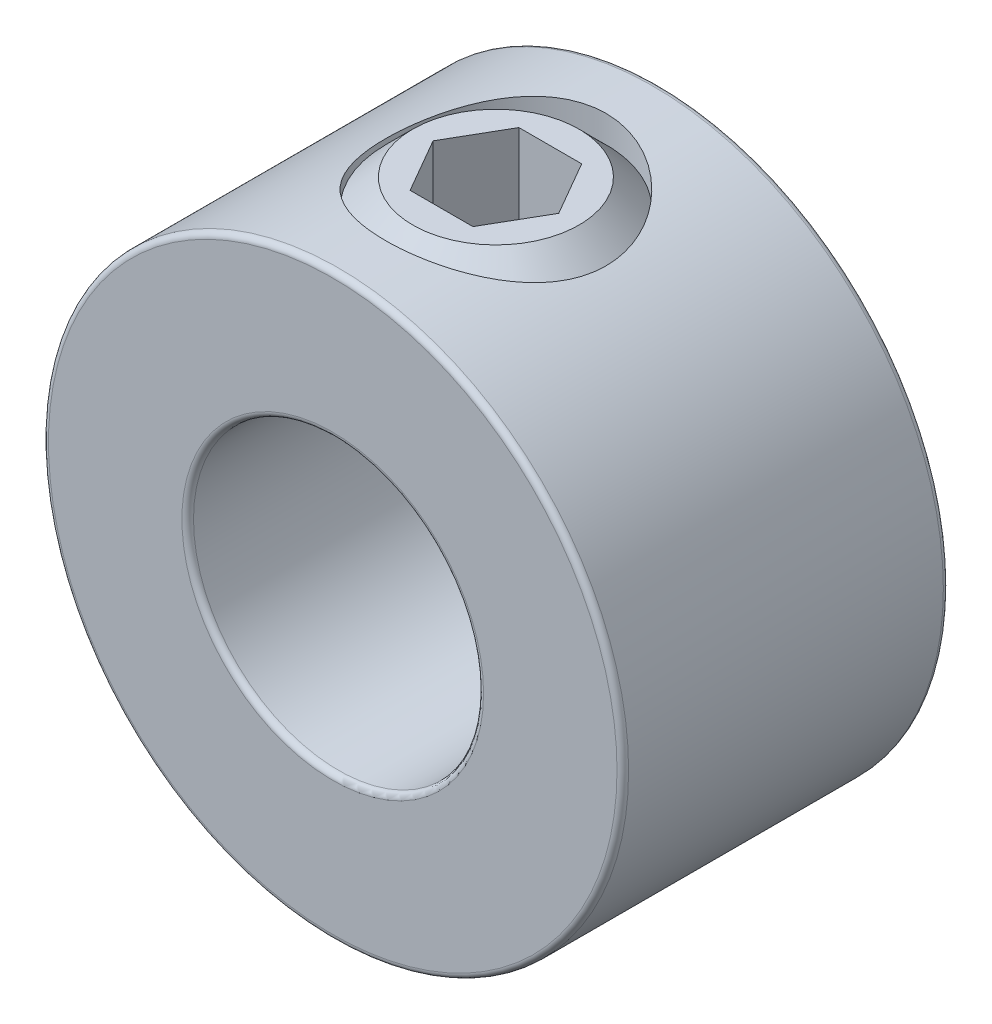
SolidWorks part; units mm, degrees
ref_plane "Front Plane" through (0, 0, 0) normal (0, 0, 1) x (1, 0, 0)
ref_plane "Top Plane" through (0, 0, 0) normal (0, 1, 0) x (1, 0, 0)
ref_plane "Right Plane" through (0, 0, 0) normal (1, 0, 0) x (0, 0, -1)
sketch "Sketch1" plane through (0, 0, 0) normal (0, 0, 1) x (1, 0, 0)
  circle A0 centre (0, 0) radius 6.35
  circle A1 centre (0, 0) radius 3.175
  point P4 (6.35, 0)
  dimension "Bore Dia" = 6.35
  dimension "OD" = 12.7
extrude "Extrude1" add sketch "Sketch1" along normal mid plane 7.1437
sketch "Sketch2" plane through (41.275, 0, 0) normal (0, -1, 0) x (0, 0, -1)
  line L0 (3.5719, -41.275) -> (-3.5719, -41.275) construction
  line L1 (-3.5719, -34.925) -> (-3.5719, -47.625) construction
  line L2 (3.5719, -47.625) -> (3.5719, -34.925) construction
  circle A0 centre (0, -41.275) radius 2.413
  point P7 (0, -43.688)
  dimension "Set Screw Dia" = 4.826
extrude "Cut-Extrude1" cut sketch "Sketch2" against normal through all
fillet "Fillet1" radius 0.127 4 edges at (3.175, 0, -3.5719) (3.175, 0, 3.5719) (6.35, 0, -3.5719) (6.35, 0, 3.5719)
sketch "Sketch3" plane through (0, 0, 0) normal (0, 0, 1) x (1, 0, 0)
  line L0 (-1.8198, 3.175) -> (-0.7119, 3.175)
  line L1 (0, 3.8869) -> (-0.7119, 3.175)
  line L2 (0, 3.8869) -> (0, 6.35)
  line L3 (0, 6.35) -> (-1.8198, 6.35)
  line L4 (-2.413, 3.7682) -> (-2.413, 5.7568)
  line L5 (0, 3.175) -> (0, 0) construction
  line L6 (-2.413, 3.7682) -> (-2.413, 3.175) construction
  line L7 (-2.413, 3.175) -> (-1.8198, 3.175) construction
  line L8 (-2.413, 5.7568) -> (-2.413, 6.35) construction
  line L9 (-1.8198, 3.175) -> (-2.413, 3.7682)
  line L10 (-2.413, 5.7568) -> (-1.8198, 6.35)
  line L11 (-2.413, 6.35) -> (-1.8198, 6.35) construction
  line L12 (-0.7119, 3.175) -> (0, 3.175) construction
  line L13 (0, 3.175) -> (0, 3.8869) construction
  circle A1 centre (0, 0) radius 3.175 construction
  dimension "D1" = 0.7119
  dimension "D2" = 0.5932
  dimension "Screw Length" = 3.175
revolve "Revolve1" add sketch "Sketch3" angle 360 about L5
sketch "Sketch4" plane through (3.3734, 6.35, 0) normal (0, -1, 0) x (0, 0, -1)
  line L1 (0, -1.9986) -> (-1.1906, -2.686)
  line L2 (-1.1906, -2.686) -> (-1.1906, -4.0608)
  line L3 (-1.1906, -4.0608) -> (0, -4.7483)
  line L4 (0, -4.7483) -> (1.1906, -4.0608)
  line L5 (1.1906, -4.0608) -> (1.1906, -2.686)
  line L6 (1.1906, -2.686) -> (0, -1.9986)
  circle A0 centre (0, -3.3734) radius 1.1906 construction
  circle A1 centre (0, -3.3734) radius 1.3748 construction
  dimension "D1" = 2.7496
  dimension "Hex Size" = 2.3813
extrude "Cut-Extrude2" cut sketch "Sketch4" along normal blind 2.3813
ref_axis "Axis1" through (0, 6.35, 0) along (0, -1, 0)
equation "\"D1@Fillet1\" = \"OD@Sketch1\"*.01"
equation "\"D1@Cut-Extrude2\" = \"Hex Size@Sketch4\""
equation "\"D2@Sketch3\" =(\"Set Screw Dia@Sketch2\"-\"D1@Sketch4\")/3.5"
equation "\"D1@Sketch3\" = \"D2@Sketch3\"*1.2"
